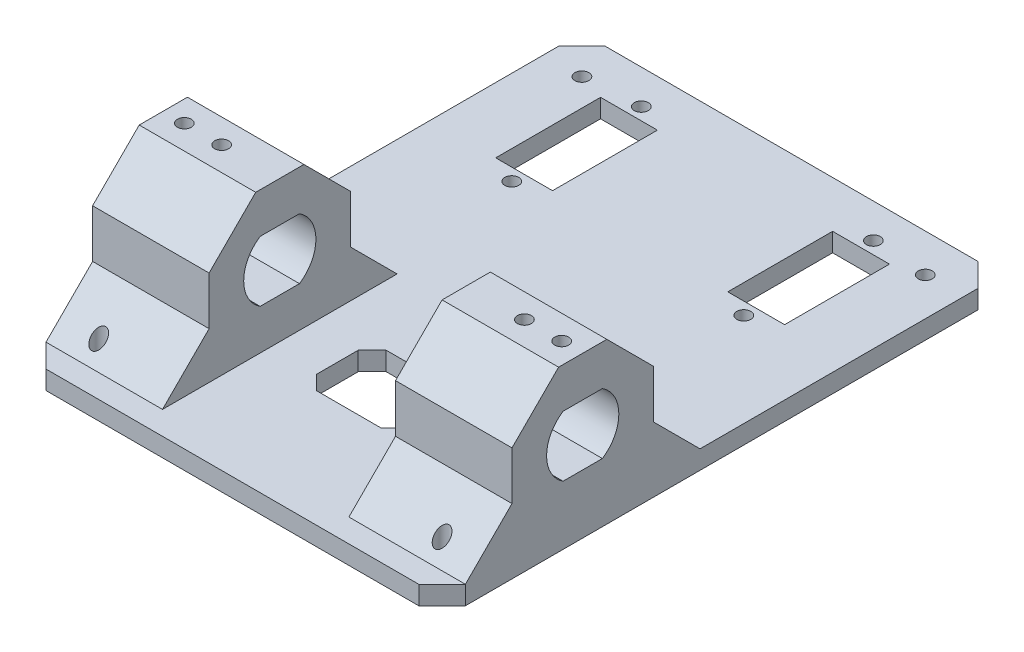
SolidWorks part; units mm, degrees
ref_plane "Front Plane" through (0, 0, 0) normal (0, 0, 1) x (1, 0, 0)
ref_plane "Top Plane" through (0, 0, 0) normal (0, 1, 0) x (1, 0, 0)
ref_plane "Right Plane" through (0, 0, 0) normal (1, 0, 0) x (0, 0, -1)
sketch "Sketch1" plane through (0, 0, 0) normal (0, 1, 0) x (1, 0, 0)
  line L5 (-45, 60) -> (45, 60)
  line L6 (-45, 60) -> (-45, -60)
  line L7 (-45, -60) -> (45, -60)
  line L12 (45, 60) -> (45, -60)
  line L13 (-45, 60) -> (45, -60) construction
  line L31 (-45, -60) -> (45, 60) construction
  point P0 (0, 0)
  dimension "D1" = 90
  dimension "D2" = 120
extrude "Boss-Extrude2" add sketch "Sketch1" along normal blind 4 contours L6 L5 L12 L7
sketch "Sketch5" plane through (0, 4, 0) normal (0, 1, 0) x (1, 0, 0)
  line L0 (-45, 60) -> (45, 60) construction
  line L1 (-31, 50) -> (-18.8, 50)
  line L2 (-31, 50) -> (-31, 27.5)
  line L3 (-31, 27.5) -> (-18.8, 27.5)
  line L4 (-18.8, 50) -> (-18.8, 27.5)
  line L5 (-31, 50) -> (-18.8, 27.5) construction
  line L6 (-31, 27.5) -> (-18.8, 50) construction
  line L7 (-45, 60) -> (-45, -60) construction
  line L8 (0, -2.2) -> (0, 2.2) construction
  line L9 (31, 27.5) -> (18.8, 50) construction
  line L10 (31, 50) -> (18.8, 27.5) construction
  line L11 (18.8, 50) -> (18.8, 27.5)
  line L12 (31, 27.5) -> (18.8, 27.5)
  line L13 (31, 50) -> (31, 27.5)
  line L14 (31, 50) -> (18.8, 50)
  point P0 (-24.9, 38.75)
  point P15 (24.9, 38.75)
  dimension "D1" = 10
  dimension "D2" = 14
  dimension "D3" = 12.2
  dimension "D4" = 22.5
extrude "Cut-Extrude1" cut sketch "Sketch5" against normal through all
sketch "Sketch10" plane through (0, 0, 0) normal (1, 0, 0) x (0, 0, -1)
  line L0 (60, 4) -> (-60, 4) construction
  line L1 (-45, 4) -> (-14.65, 4)
  line L2 (-45, 4) -> (-45, 34.35)
  line L3 (-45, 34.35) -> (-14.65, 34.35)
  line L4 (-14.65, 4) -> (-14.65, 34.35)
  line L5 (-34.0455, 25.675) -> (-25.6045, 25.675)
  line L6 (-60, 4) -> (-60, 0) construction
  line L7 (-45, 34.35) -> (-14.65, 4) construction
  line L8 (-45, 4) -> (-14.65, 34.35) construction
  line L9 (-39.1014, 19.175) -> (-19.2295, 19.175) construction
  line L10 (-34.0455, 12.675) -> (-25.6045, 12.675)
  circle A0 centre (-29.825, 19.175) radius 7.75
  dimension "D3" = 15.5
  dimension "D1" = 30.35
  dimension "D2" = 15
  dimension "D5" = 13
extrude "Boss-Extrude4" add sketch "Sketch10" against normal blind 25 from surface contours L1 L4 L3 L2 A0 | L5 A0 | L10 A0 region at (0, 19.175, 44.5708) region at (0, 26.1786, 29.825) region at (0, 12.1714, 29.825) starting at face at (45, 2, 0)
extrude "Boss-Extrude5" add sketch "Sketch10<4>" along normal blind 25 from surface contours L1 L4 L3 L2 A0 | L5 A0 | L10 A0 region at (0, 19.175, 44.5708) region at (0, 26.1786, 29.825) region at (0, 12.1714, 29.825) starting at face at (-45, 2, 0)
sketch "Sketch10<4>" plane through (0, 0, 0) normal (1, 0, 0) x (0, 0, -1) same geometry as "Sketch10"
chamfer "Chamfer6" distance 5 angle 45 4 edges at (45, 2, -60) (-45, 2, -60) (-45, 2, 60) (45, 2, 60)
chamfer "Chamfer7" distance 10 angle 45 8 edges at (32.5, 4, 45) (32.5, 4, 14.65) (32.5, 34.35, 14.65) (32.5, 34.35, 45) (-32.5, 34.35, 45) (-32.5, 34.35, 14.65) (-32.5, 4, 14.65) (-32.5, 4, 45)
sketch "Sketch13" plane through (0, 0, 0) normal (0, -1, 0) x (1, 0, 0)
  line L4 (-42.5, 57.5) -> (-16.868, 31.868) construction
  line L6 (-40, 60) -> (-45, 55) construction
  point P7 (-36.8431, 51.8431)
  point P14 (-42.5, 57.5)
  dimension "D1" = 8
hole_wizard "Ø3.0 (3) Diameter Hole2" positions "Sketch13" profile "Sketch14" hole size "Ø3.0" standard "ANSI Metric" end condition through all
sketch "Sketch14" plane through (-36.8431, 0, 51.8431) normal (1, 0, 0) x (0, 0, -1)
  line L0 (0, 0) -> (0, 34.35)
  line L1 (0, 34.35) -> (1.5, 34.35)
  line L2 (1.5, 34.35) -> (1.5, 0)
  line L5 (1.5, 0) -> (0, 0)
  line L11 (0, -6.35) -> (0, 107.95) construction
  dimension "Thru Hole Dia." = 3
  dimension "Thru Hole Depth" = 34.35
mirror "Mirror9" about plane through (0, 0, 0) normal (0, 0, 1) of "Ø3.0 (3) Diameter Hole2" second plane through (0, 0, 0) second plane normal (1, 0, 0)
sketch "Sketch15" plane through (0, 0, 0) normal (0, -1, 0) x (1, 0, 0)
  line L0 (-31, -38.75) -> (-18.8, -38.75) construction
  line L1 (-31, -50) -> (-31, -27.5) construction
  line L2 (-18.8, -27.5) -> (-18.8, -50) construction
  point P0 (-24.9, -24.85)
  point P1 (-24.9, -52.65)
  point P3 (-24.9, -38.75)
  dimension "D1" = 13.9
  dimension "D2" = 13.9
hole_wizard "Ø3.0 (3) Diameter Hole3" positions "Sketch15" profile "Sketch16" hole size "Ø3.0" standard "ANSI Metric" end condition through all
sketch "Sketch16" plane through (-24.9, 0, -24.85) normal (1, 0, 0) x (0, 0, -1)
  line L0 (0, 0) -> (0, 34.35)
  line L1 (0, 34.35) -> (1.5, 34.35)
  line L2 (1.5, 34.35) -> (1.5, 0)
  line L5 (1.5, 0) -> (0, 0)
  line L11 (0, -6.35) -> (0, 107.95) construction
  dimension "Thru Hole Dia." = 3
  dimension "Thru Hole Depth" = 34.35
mirror "Mirror10" about plane through (0, 0, 0) normal (1, 0, 0) of "Ø3.0 (3) Diameter Hole3"
sketch "Sketch17" plane through (0, 34.35, 0) normal (0, 1, 0) x (1, 0, 0)
  line L3 (-45, -29.825) -> (-27.9696, -29.825) construction
  line L4 (-45, -35) -> (-45, -24.65) construction
  line L6 (-27.9696, -35) -> (-27.9696, -24.65) construction
  point P1 (-40.4848, -29.825)
  point P20 (-32.4848, -29.825)
  point P24 (-36.4848, -29.825)
  dimension "D1" = 4
  dimension "D2" = 4
hole_wizard "Ø3.0 (3) Diameter Hole5" positions "Sketch17" profile "Sketch20" hole size "Ø3.0" standard "ANSI Metric"
sketch "Sketch20" plane through (-32.4848, 34.35, 29.825) normal (1, 0, 0) x (0, 0, 1)
  line L0 (0, 0) -> (0, 10)
  line L1 (0, 10) -> (1.5, 9.0987)
  line L2 (1.5, 9.0987) -> (1.5, 0)
  line L5 (1.5, 0) -> (0, 0)
  line L10 (0, 10) -> (-1.5, 9.0987) construction
  line L11 (0, -6.35) -> (0, 107.95) construction
  dimension "Hole Dia." = 3
  dimension "Hole Depth" = 10
  dimension "Drill Angle" = 118
mirror "Mirror11" about plane through (0, 0, 0) normal (1, 0, 0) of "Ø3.0 (3) Diameter Hole5"
sketch "Sketch21" plane through (0, 4, 0) normal (0, 1, 0) x (1, 0, 0)
  line L0 (0, 0) -> (0, -60) construction
  line L1 (-10, -20) -> (10, -20)
  line L2 (-10, -20) -> (-10, -35)
  line L3 (-10, -35) -> (10, -35)
  line L4 (10, -20) -> (10, -35)
  line L5 (-40, -60) -> (40, -60) construction
  point P9 (0, -35)
  dimension "D1" = 15
  dimension "D2" = 20
  dimension "D3" = 25
extrude "Cut-Extrude2" cut sketch "Sketch21" against normal through all
chamfer "Chamfer8" distance 3 angle 45 4 edges at (10, 2, 35) (10, 2, 20) (-10, 2, 20) (-10, 2, 35)
